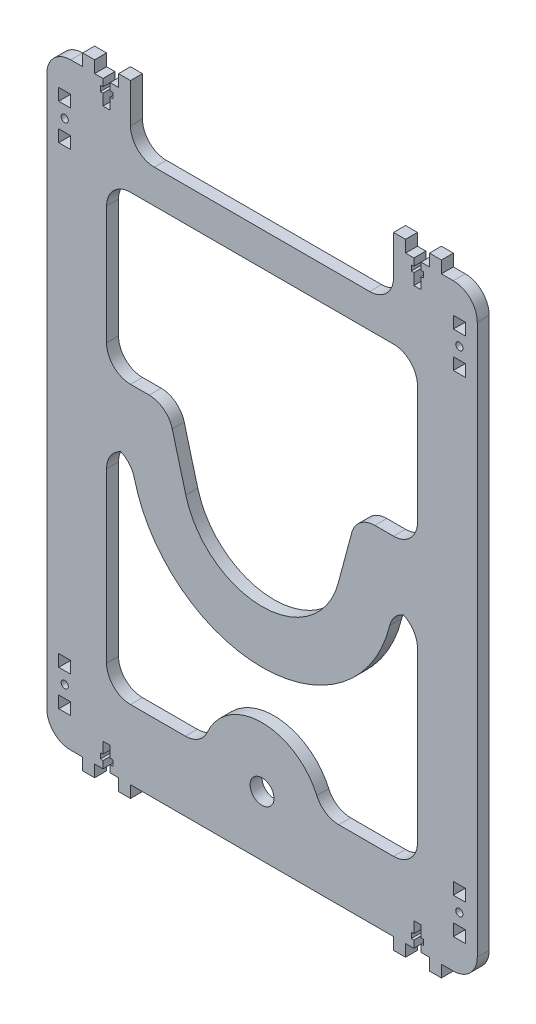
SolidWorks part; units mm, degrees
ref_plane "Front Plane" through (0, 0, 0) normal (0, 0, 1) x (1, 0, 0)
ref_plane "Top Plane" through (0, 0, 0) normal (0, 1, 0) x (1, 0, 0)
ref_plane "Right Plane" through (0, 0, 0) normal (1, 0, 0) x (0, 0, -1)
sketch "Sketch1" plane through (0, 0, 0) normal (0, 0, 1) x (1, 0, 0)
  line L0 (0, 0) -> (187.0096, 0) construction
  line L1 (-90, 125) -> (-55, 125) construction
  line L2 (-90, 125) -> (-90, -125)
  line L3 (-90, -125) -> (90, -125)
  line L4 (90, 125) -> (90, -125)
  line L5 (0, 0) -> (0, 134.5508) construction
  line L6 (-31.8756, -8.541) -> (-39.5231, 20)
  line L7 (-65, 89.5396) -> (65, 89.5396)
  line L8 (65, 89.5396) -> (65, 0) construction
  line L9 (65, 0) -> (-65, 0) construction
  line L10 (-65, 0) -> (-65, 89.5396) construction
  line L11 (-65, 0) -> (-20, 0) construction
  line L12 (20, 0) -> (65, 0) construction
  line L13 (82.5, 125) -> (82.5, -125) construction
  line L14 (0, 0) -> (0, -125) construction
  line L21 (-39.5231, 20) -> (-65, 20)
  line L22 (-65, 20) -> (-65, 89.5396)
  line L23 (65, 20) -> (65, 89.5396)
  line L24 (39.5231, 20) -> (65, 20)
  line L26 (-90, 125) -> (-55, 125)
  line L27 (31.8756, -8.541) -> (39.5231, 20)
  line L28 (-55, 125) -> (-55, 103.5988)
  line L29 (-55, 103.5988) -> (55, 103.5988)
  line L30 (55, 103.5988) -> (55, 125)
  line L31 (55, 125) -> (90, 125) construction
  line L32 (55, 125) -> (90, 125)
  line L33 (-54.7172, -5.5707) -> (-65, -5.5707)
  line L34 (-65, -5.5707) -> (-65, -95.958)
  line L35 (-65, -95.958) -> (-24.6711, -95.958)
  line L36 (54.7172, -5.5707) -> (65, -5.5707)
  line L37 (65, -5.5707) -> (65, -95.958)
  line L38 (65, -95.958) -> (24.6711, -95.958)
  circle A1 centre (0, -100) radius 5
  circle A2 centre (0, 0) radius 33 construction
  arc A3 (31.8756, -8.541) -> (-31.8756, -8.541) centre (0, 0) cw
  circle A4 centre (0, 0) radius 55 construction
  circle A5 centre (0, -100) radius 25 construction
  arc A6 (24.6711, -95.958) -> (-24.6711, -95.958) centre (0, -100) ccw
  arc A7 (-54.7172, -5.5707) -> (54.7172, -5.5707) centre (0, 0) ccw
  line B0 (82.5, 107.5) -> (82.5, 97.5) construction
  line B1 (80, 107.5) -> (80, 112.5)
  line B2 (80, 107.5) -> (85, 107.5)
  line B3 (85, 107.5) -> (85, 112.5)
  line B4 (80, 112.5) -> (85, 112.5)
  line B5 (80, 97.5) -> (80, 92.5)
  line B6 (80, 97.5) -> (85, 97.5)
  line B7 (85, 97.5) -> (85, 92.5)
  line B8 (80, 92.5) -> (85, 92.5)
  line B9 (82.5, 102.5) -> (75.5276, 102.5) construction
  circle B10 centre (82.5, 102.5) radius 1.5
  line B11 (82.5, -107.5) -> (82.5, -97.5) construction
  line B12 (80, -107.5) -> (80, -112.5)
  line B13 (80, -107.5) -> (85, -107.5)
  line B14 (85, -107.5) -> (85, -112.5)
  line B15 (80, -112.5) -> (85, -112.5)
  line B16 (80, -97.5) -> (80, -92.5)
  line B17 (80, -97.5) -> (85, -97.5)
  line B18 (85, -97.5) -> (85, -92.5)
  line B19 (80, -92.5) -> (85, -92.5)
  line B20 (82.5, -102.5) -> (75.5276, -102.5) construction
  circle B21 centre (82.5, -102.5) radius 1.5
  line B22 (-82.5, 107.5) -> (-82.5, 97.5) construction
  line B23 (-80, 107.5) -> (-80, 112.5)
  line B24 (-80, 107.5) -> (-85, 107.5)
  line B25 (-85, 107.5) -> (-85, 112.5)
  line B26 (-80, 112.5) -> (-85, 112.5)
  line B27 (-80, 97.5) -> (-80, 92.5)
  line B28 (-80, 97.5) -> (-85, 97.5)
  line B29 (-85, 97.5) -> (-85, 92.5)
  line B30 (-80, 92.5) -> (-85, 92.5)
  line B31 (-82.5, 102.5) -> (-75.5276, 102.5) construction
  circle B32 centre (-82.5, 102.5) radius 1.5
  line B33 (-82.5, -107.5) -> (-82.5, -97.5) construction
  line B34 (-80, -107.5) -> (-80, -112.5)
  line B35 (-80, -107.5) -> (-85, -107.5)
  line B36 (-85, -107.5) -> (-85, -112.5)
  line B37 (-80, -112.5) -> (-85, -112.5)
  line B38 (-80, -97.5) -> (-80, -92.5)
  line B39 (-80, -97.5) -> (-85, -97.5)
  line B40 (-85, -97.5) -> (-85, -92.5)
  line B41 (-80, -92.5) -> (-85, -92.5)
  line B42 (-82.5, -102.5) -> (-75.5276, -102.5) construction
  circle B43 centre (-82.5, -102.5) radius 1.5
  line B44 (-67.6, -122) -> (-67.6, -119.7)
  line B45 (-63.5, -119.7) -> (-63.5, -115)
  line B46 (-66.5, -115) -> (-66.5, -119.7)
  line B47 (-67.6, -119.7) -> (-66.5, -119.7)
  line B48 (-65, -125) -> (-65, -113.7792) construction
  line B49 (-66.5, -125) -> (-70, -125)
  line B50 (-70, -130) -> (-75, -130)
  line B51 (-75, -130) -> (-75, -125)
  line B52 (-70, -130) -> (-70, -125)
  line B53 (-63.5, -125) -> (-60, -125)
  line B54 (-60, -125) -> (-60, -130)
  line B55 (-60, -130) -> (-55, -130)
  line B56 (-55, -130) -> (-55, -125)
  line B57 (-66.5, -125) -> (-63.5, -125) construction
  line B58 (-63.5, -125) -> (-63.5, -122)
  line B59 (-63.5, -119.7) -> (-62.4, -119.7)
  line B60 (-62.4, -122) -> (-63.5, -122)
  line B61 (-63.5, -115) -> (-66.5, -115)
  line B62 (-66.5, -122) -> (-67.6, -122)
  line B63 (-62.4, -119.7) -> (-62.4, -122)
  line B64 (-66.5, -122) -> (-66.5, -125)
  line B65 (-65, -115) -> (-65, -125) construction
  line B66 (62.4, -122) -> (62.4, -119.7)
  line B67 (66.5, -119.7) -> (66.5, -115)
  line B68 (63.5, -115) -> (63.5, -119.7)
  line B69 (62.4, -119.7) -> (63.5, -119.7)
  line B70 (65, -125) -> (65, -113.7792) construction
  line B71 (63.5, -125) -> (60, -125)
  line B72 (60, -130) -> (55, -130)
  line B73 (55, -130) -> (55, -125)
  line B74 (60, -130) -> (60, -125)
  line B75 (66.5, -125) -> (70, -125)
  line B76 (70, -125) -> (70, -130)
  line B77 (70, -130) -> (75, -130)
  line B78 (75, -130) -> (75, -125)
  line B79 (63.5, -125) -> (66.5, -125) construction
  line B80 (66.5, -125) -> (66.5, -122)
  line B81 (66.5, -119.7) -> (67.6, -119.7)
  line B82 (67.6, -122) -> (66.5, -122)
  line B83 (66.5, -115) -> (63.5, -115)
  line B84 (63.5, -122) -> (62.4, -122)
  line B85 (67.6, -119.7) -> (67.6, -122)
  line B86 (63.5, -122) -> (63.5, -125)
  line B87 (65, -115) -> (65, -125) construction
  line B88 (67.6, 122) -> (67.6, 119.7)
  line B89 (63.5, 119.7) -> (63.5, 115)
  line B90 (66.5, 115) -> (66.5, 119.7)
  line B91 (67.6, 119.7) -> (66.5, 119.7)
  line B92 (65, 125) -> (65, 113.7792) construction
  line B93 (66.5, 125) -> (70, 125)
  line B94 (70, 130) -> (75, 130)
  line B95 (75, 130) -> (75, 125)
  line B96 (70, 130) -> (70, 125)
  line B97 (63.5, 125) -> (60, 125)
  line B98 (60, 125) -> (60, 130)
  line B99 (60, 130) -> (55, 130)
  line B100 (55, 130) -> (55, 125)
  line B101 (66.5, 125) -> (63.5, 125) construction
  line B102 (63.5, 125) -> (63.5, 122)
  line B103 (63.5, 119.7) -> (62.4, 119.7)
  line B104 (62.4, 122) -> (63.5, 122)
  line B105 (63.5, 115) -> (66.5, 115)
  line B106 (66.5, 122) -> (67.6, 122)
  line B107 (62.4, 119.7) -> (62.4, 122)
  line B108 (66.5, 122) -> (66.5, 125)
  line B109 (65, 115) -> (65, 125) construction
  line B110 (-62.4, 122) -> (-62.4, 119.7)
  line B111 (-66.5, 119.7) -> (-66.5, 115)
  line B112 (-63.5, 115) -> (-63.5, 119.7)
  line B113 (-62.4, 119.7) -> (-63.5, 119.7)
  line B114 (-65, 125) -> (-65, 113.7792) construction
  line B115 (-63.5, 125) -> (-60, 125)
  line B116 (-60, 130) -> (-55, 130)
  line B117 (-55, 130) -> (-55, 125)
  line B118 (-60, 130) -> (-60, 125)
  line B119 (-66.5, 125) -> (-70, 125)
  line B120 (-70, 125) -> (-70, 130)
  line B121 (-70, 130) -> (-75, 130)
  line B122 (-75, 130) -> (-75, 125)
  line B123 (-63.5, 125) -> (-66.5, 125) construction
  line B124 (-66.5, 125) -> (-66.5, 122)
  line B125 (-66.5, 119.7) -> (-67.6, 119.7)
  line B126 (-67.6, 122) -> (-66.5, 122)
  line B127 (-66.5, 115) -> (-63.5, 115)
  line B128 (-63.5, 122) -> (-62.4, 122)
  line B129 (-67.6, 119.7) -> (-67.6, 122)
  line B130 (-63.5, 122) -> (-63.5, 125)
  line B131 (-65, 115) -> (-65, 125) construction
  dimension "D8" = 50
  dimension "D10" = 10
  dimension "D2" = 33
  dimension "D13" = 110
  dimension "D3" = 250
  dimension "D4" = 180
  dimension "D5" = 105
  dimension "D6" = 25
  dimension "D7" = 20
  dimension "D9" = 22.5
  dimension "D11" = 25
  dimension "D12" = 7.5
sketch_block_instance "Trou M3 plots 5mm-7"
sketch_block "Trou M3 plots 5mm" parameters "D2"=3, "D1"=5, "D3"=5, "D4"=10
sketch_block_instance "Trou M3 plots 5mm-8"
sketch_block_instance "Trou M3 plots 5mm-9"
sketch_block_instance "Trou M3 plots 5mm-10"
sketch_block_instance "Insert M3 plots ep 5mm-1"
sketch_block "Insert M3 plots ep 5mm" parameters "D1"=10, "D2"=5, "D3"=5
sketch_block_instance "Decoupe Insert M3-4"
sketch_block "Decoupe Insert M3" parameters "D1"=5.2, "D2"=3, "D3"=2.3, "D4"=3, "D5"=10
sketch_block_instance "Insert M3 plots ep 5mm-2"
sketch_block_instance "Insert M3 plots ep 5mm-3"
sketch_block_instance "Insert M3 plots ep 5mm-5"
extrude "Boss-Extrude1" add sketch "Sketch1" along normal blind 5 contours B130 B128 B110 B113 B112 B127 B111 B125 B129 B126 B124 L26 L2 L3 B64 B62 B44 B47 B46 B61 B45 B59 B63 B60 B58 B86 B84 B66 B69 B68 B83 B67 B81 B85 B82 B80 L4 | B50 B52 L3 B51 | B55 B56 L3 B54 | B72 B74 L3 B73 | B77 B78 L3 B76 | B121 B122 L26 B120 | B116 B118 L26 B117 | B99 B100 L26 B98 | B94 B96 L26 B95 region at (-82.5, 121.9194, 0) region at (-72.5, 127.5, 0) region at (-72.5, -127.5, 0) region at (-57.5, 127.5, 0) region at (-57.5, -127.5, 0) region at (57.5, -127.5, 0) region at (57.5, 127.5, 0) region at (72.5, -127.5, 0) region at (72.5, 127.5, 0)
fillet "Fillet1" radius 10 20 edges at (-90, -125, 2.5) (90, -125, 2.5) (-90, 125, 2.5) (90, 125, 2.5) (-55, 103.5988, 2.5) (55, 103.5988, 2.5) (24.6711, -95.958, 2.5) (-24.6711, -95.958, 2.5) (-65, -95.958, 2.5) (65, -95.958, 2.5) (65, -5.5707, 2.5) (54.7172, -5.5707, 2.5) (-54.7172, -5.5707, 2.5) (-65, -5.5707, 2.5) (65, 89.5396, 2.5) (-65, 89.5396, 2.5) (65, 20, 2.5) (-65, 20, 2.5) (39.5231, 20, 2.5) (-39.5231, 20, 2.5)
